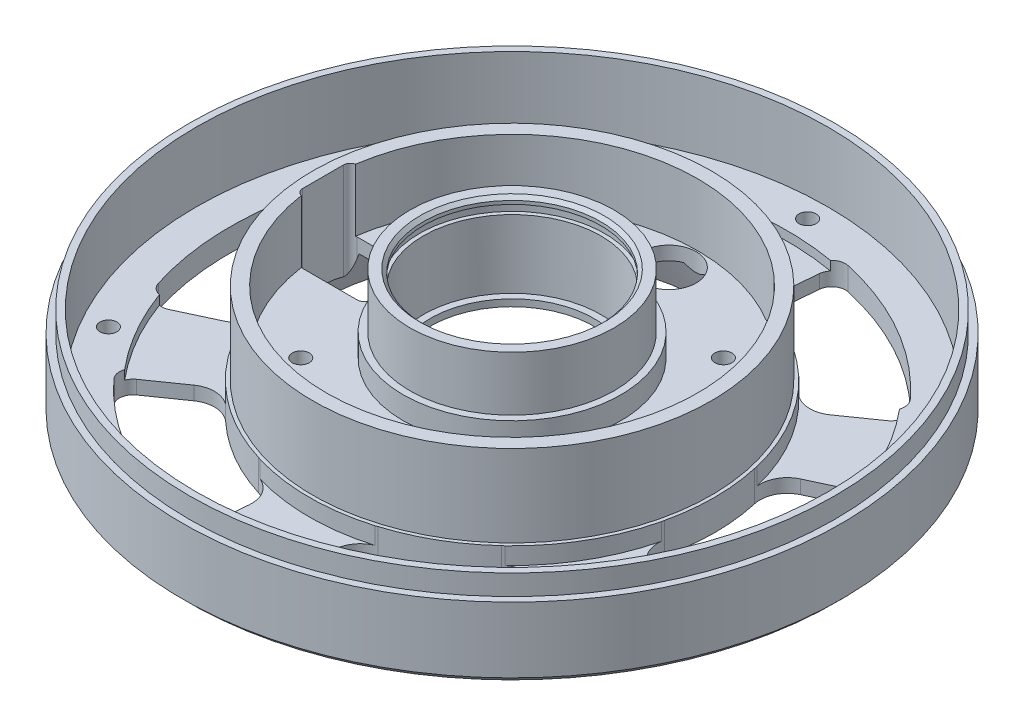
SolidWorks part; units mm, degrees
material "5052-H32"
ref_plane "Front Plane" through (0, 0, 0) normal (0, 0, 1) x (1, 0, 0)
ref_plane "Top Plane" through (0, 0, 0) normal (0, 1, 0) x (1, 0, 0)
ref_plane "Right Plane" through (0, 0, 0) normal (1, 0, 0) x (0, 0, -1)
ref_axis "Axis1" through (0, 0, 0) along (0, 1, 0)
sketch "Sketch1" plane through (0, 0, 0) normal (0, 0, 1) x (1, 0, 0)
  line L0 (0, 0) -> (0, -50000) construction
  line L1 (-13.02, 8.15) -> (-13.02, -4.15)
  line L2 (-13.02, -4.15) -> (-12.02, -4.15)
  line L4 (45.1, 8.15) -> (-45.1, 8.15) construction
  line L5 (-12.75, -4.15) -> (12.75, -4.15) construction
  line L7 (-13.02, 8.15) -> (-14.98, 8.15)
  line L8 (-14.98, 8.15) -> (-14.98, -3.15)
  line L9 (-14.98, -3.15) -> (-28.25, -3.15)
  line L10 (-12.02, -5.15) -> (-28.25, -5.15)
  line L12 (-28.25, -5.15) -> (-28.25, -3.15)
  line L13 (-29.25, 6) -> (-29.25, -6) construction
  line L16 (-12.02, -4.15) -> (-12.02, -5.15)
  dimension "D1" = 1
  dimension "D2" = 29.96
  dimension "D3" = 2
  dimension "D4" = 1
  dimension "D5" = 1
  dimension "D6" = 26.04
revolve "Revolve1" add sketch "Sketch1" angle 360 about L0
sketch "Sketch4" plane through (0, 0, 0) normal (0, 0, 1) x (1, 0, 0)
  line L1 (-29.75, -8.5) -> (-40.35, -8.5)
  line L2 (-46.35, -7.15) -> (-46.35, 3)
  line L3 (-46.35, 3) -> (-47.35, 3)
  line L4 (-47.35, 3) -> (-47.35, 0)
  line L5 (-47.35, 0) -> (-48.35, 0)
  line L6 (-48.35, 0) -> (-48.35, -9.6235)
  line L7 (-47.4735, -10.5) -> (-28.75, -10.5)
  line L8 (-28.75, -10.5) -> (-26.75, -5.15)
  line L9 (-29.75, -8.5) -> (-29.75, -6)
  line L10 (-26.75, -5.15) -> (-26.75, -3.15)
  line L12 (-48.35, -9.6235) -> (-47.4735, -10.5)
  line L13 (-45.1, 8.15) -> (-45.1, -6.15) construction
  line L14 (-46.35, -7.15) -> (-40.35, -7.15)
  line L15 (-40.35, -7.15) -> (-40.35, -8.5)
  line L16 (-45.1, -6.15) -> (45.1, -6.15) construction
  line L18 (-44.85, -7.15) -> (-44.85, -10.5) construction
  line L20 (-41.85, -7.15) -> (-41.85, -10.5) construction
  line L21 (-30.25, -6) -> (30.25, -6) construction
  line L22 (-29.75, -6) -> (-29.23, -6)
  line L23 (-29.25, -6) -> (29.25, -6) construction
  line L24 (-29.23, -6) -> (-29.23, -3.15)
  line L25 (-29.23, -3.15) -> (-26.75, -3.15)
  line L26 (28.25, -3.15) -> (-28.25, -3.15) construction
  line L27 (-39.5, -7.5) -> (39.5, -7.5) construction
  line L28 (0, 0) -> (0, 50000) construction
  line L29 (-30.25, -6) -> (-30.25, -7.5) construction
  line L33 (-28.25, -5.15) -> (28.25, -5.15) construction
  dimension "D1" = 2
  dimension "D2" = 3
  dimension "D3" = 1
  dimension "D4" = 2
  dimension "D5" = 0.5
  dimension "D6" = 1
  dimension "D7" = 1.25
  dimension "D8" = 135
  dimension "D9" = 3
  dimension "D10" = 1.5
  dimension "D11" = 1.5
  dimension "D12" = 2
  dimension "D13" = 1
  dimension "D14" = 58.46
revolve "Revolve2" add sketch "Sketch4" angle 360 about axis through (0, 0, 0) along (0, 1, 0)
sketch "Sketch6" plane through (0, 0, 0) normal (0, 0, 1) x (1, 0, 0)
  line L0 (-29.23, 6) -> (-27.23, 6)
  line L1 (-27.23, 6) -> (-27.23, -3.15)
  line L2 (-27.23, -3.15) -> (-29.23, -3.15)
  line L3 (-29.23, -3.15) -> (-29.23, 6)
  line L4 (29.25, 6) -> (-29.25, 6) construction
  line L6 (29.23, -3.15) -> (-29.23, -3.15) construction
  dimension "D1" = 2
revolve "Revolve3" add sketch "Sketch6" angle 360 about axis through (0, 0, 0) along (0, 1, 0)
sketch "Sketch7" plane through (0, 0, 0) normal (0, 0, 1) x (1, 0, 0)
  line L0 (40.35, -8.5) -> (-40.35, -8.5) construction
  line L1 (-29.58, -6) -> (-29.23, -6)
  line L2 (-29.73, -6.15) -> (-29.73, -8.5)
  line L3 (-29.73, -8.5) -> (-29.23, -8.5)
  line L4 (-29.23, -6) -> (-29.23, -8.5)
  line L5 (-29.23, 6) -> (-29.23, -6) construction
  line L6 (-29.58, -6) -> (-29.73, -6.15)
  line L7 (29.75, -8.5) -> (-29.75, -8.5) construction
  line L8 (-31.759, -6.15) -> (-25.7399, -6.15) construction
  line L13 (-30.25, -6) -> (30.25, -6) construction
  dimension "D1" = 135
  dimension "D2" = 0.5
revolve "Revolve4" add sketch "Sketch7" angle 360 about axis through (0, 0, 0) along (0, 1, 0)
sketch "Sketch8" plane through (0, -5.15, 0) normal (0, -1, 0) x (1, 0, 0)
  circle A0 centre (-15.5, 15.5) radius 3.5
  circle A1 centre (15.5, 15.5) radius 3.5
  circle A2 centre (15.5, -15.5) radius 3.5
  circle A3 centre (-15.5, -15.5) radius 3.5
  dimension "D1" = 7
sketch "Sketch10" plane through (0, 0, 0) normal (0, 0, 1) x (1, 0, 0)
  line L0 (-15.25, 0.15) -> (15.25, 0.15) construction
  line L1 (-14.98, -3.15) -> (-15.98, -3.15)
  line L2 (-14.98, -3.15) -> (-14.98, 0.15)
  line L3 (-14.98, 0.15) -> (-15.98, 0.15)
  line L4 (-15.98, -3.15) -> (-15.98, 0.15)
  line L5 (-14.98, 8.15) -> (-14.98, -3.15) construction
  line L6 (14.98, -3.15) -> (-14.98, -3.15) construction
  dimension "D1" = 1
revolve "Revolve5" add sketch "Sketch10" angle 360 about axis through (0, 0, 0) along (0, 1, 0)
sketch "Sketch12" plane through (0, 0, 0) normal (0, 1, 0) x (1, 0, 0)
  circle A0 centre (-23, 0) radius 4
  dimension "D1" = 8
  dimension "D2" = 23
extrude "Cut-Extrude2" cut sketch "Sketch12" against normal through all
pattern_circular "CirPattern3" count 4 over 360 about axis through (0, 0, 0) along (0, 1, 0) of "Cut-Extrude2"
extrude "Boss-Extrude1" add sketch "Sketch8" along normal up to surface (3.85 mm away)
hole_wizard "M3x0.5 Tapped Hole1" positions "Sketch14" profile "Sketch15" tap size "M3x0.5" standard "ANSI Metric" end condition through all
sketch "Sketch14" plane through (0, -9, 0) normal (0, -1, 0) x (-1, 0, 0)
  point P0 (-15.5, 15.5)
  point P3 (15.5, 15.5)
  point P6 (15.5, -15.5)
  point P9 (-15.5, -15.5)
cosmetic thread "Hole Thread1" parameters "D2"=3
cosmetic thread "Hole Thread2" parameters "D2"=3
cosmetic thread "Hole Thread3" parameters "D2"=3
cosmetic thread "Hole Thread4" parameters "D2"=3
sketch "Sketch15" plane through (15.5, -9, -15.5) normal (1, 0, 0) x (0, 0, -1)
  line L0 (0, 0) -> (0, 17.15)
  line L1 (0, 17.15) -> (1.25, 17.15)
  line L2 (1.25, 17.15) -> (1.25, 0)
  line L5 (1.25, 0) -> (0, 0)
  line L11 (0, -6.35) -> (0, 107.95) construction
  dimension "Thru Tap Drill Dia." = 2.5
  dimension "Thru Tap Drill Depth" = 17.15
hole_wizard "M3x0.5 Tapped Hole3" positions "Sketch19" profile "Sketch20" tap size "M3x0.5" standard "ANSI Metric" end condition through all
sketch "Sketch19" plane through (0, -10.5, 0) normal (0, -1, 0) x (-1, 0, 0)
  line L0 (0, 0) -> (0, 43.35) construction
  line L3 (0, 0) -> (-50000, 0) construction
  circle A1 centre (0, 0) radius 43.35 construction
  circle A2 centre (0, 0) radius 40.35 construction
  point P0 (0, 43.35)
  dimension "D1" = 3
  dimension "D2" = 90
sketch "Sketch20" plane through (0, -10.5, -43.35) normal (1, 0, 0) x (0, 0, -1)
  line L0 (0, 0) -> (0, 18.65)
  line L1 (0, 18.65) -> (1.25, 18.65)
  line L2 (1.25, 18.65) -> (1.25, 0.5)
  line L3 (1.25, 0.5) -> (1.75, 0)
  line L5 (1.75, 0) -> (0, 0)
  line L6 (-1.25, 0.5) -> (-1.75, 0) construction
  line L11 (0, -6.35) -> (0, 107.95) construction
  dimension "Thru Tap Drill Dia." = 2.5
  dimension "Thru Tap Drill Depth" = 18.65
  dimension "Near C'Sink Dia." = 3.5
  dimension "Near C'Sink Angle" = 90
cosmetic thread "Hole Thread7" parameters "D2"=3
pattern_circular "CirPattern4" count 6 over 360 about axis through (0, 0, 0) along (0, 1, 0) of "M3x0.5 Tapped Hole3"
sketch "Sketch24" plane through (0, -10.5, 0) normal (0, -1, 0) x (1, 0, 0)
  line L9 (-25.6489, 5.5) -> (-44.2117, 5.5)
  line L10 (-25.6489, 5.5) -> (-25.6489, -5.5)
  line L11 (-25.6489, -5.5) -> (-44.2117, -5.5)
  line L12 (-46.2117, 3.5) -> (-46.2117, -3.5)
  arc A5 (-44.2117, -5.5) -> (-46.2117, -3.5) centre (-44.2117, -3.5) cw
  arc A6 (-44.2117, 5.5) -> (-46.2117, 3.5) centre (-44.2117, 3.5) ccw
  circle A7 centre (0, 0) radius 46.35 construction
  point P5 (-25.6489, 0)
  dimension "D2" = 2
  dimension "D1" = 11
extrude "Cut-Extrude6" [suppressed] cut sketch "Sketch24" against normal up to surface (1.5 mm away)
sketch "Sketch25" plane through (0, -10.5, 0) normal (0, -1, 0) x (1, 0, 0)
  line L5 (-25.6489, 5.5) -> (-44.2117, 5.5) construction
  line L9 (-34.6807, 5.5) -> (-44.2117, 5.5)
  line L10 (-34.6807, 5.5) -> (-34.6807, -5.5)
  line L11 (-34.6807, -5.5) -> (-44.2117, -5.5)
  line L12 (-46.2117, 3.5) -> (-46.2117, -3.5)
  line L13 (-25.6489, -5.5) -> (-44.2117, -5.5) construction
  line L14 (-46.2117, 3.5) -> (-46.2117, -3.5) construction
  arc A3 (-44.2117, -5.5) -> (-46.2117, -3.5) centre (-44.2117, -3.5) cw
  arc A4 (-44.2117, 5.5) -> (-46.2117, 3.5) centre (-44.2117, 3.5) ccw
  point P12 (-46.2117, -5.5)
  dimension "D1" = 2
extrude "Cut-Extrude7" [suppressed] cut sketch "Sketch25" against normal through all
sketch "Sketch26" plane through (0, 0, 0) normal (0, 1, 0) x (1, 0, 0)
  line L0 (0, 0) -> (-50000, 0) construction
  line L1 (31.1951, 11.1252) -> (36.6728, 13.6795)
  line L2 (31.1951, -11.1252) -> (36.6728, -13.6795)
  arc A0 (39.4249, 12.47) -> (39.4249, -12.47) centre (0, 0) cw
  arc A1 (28.9857, 6.6106) -> (28.9857, -6.6106) centre (0, 0) cw
  arc A2 (28.9857, -6.6106) -> (31.1951, -11.1252) centre (32.8856, -7.5) ccw
  arc A3 (28.9857, 6.6106) -> (31.1951, 11.1252) centre (32.8856, 7.5) cw
  circle A4 centre (0, 0) radius 46.35 construction
  arc A6 (39.4249, -12.47) -> (36.6728, -13.6795) centre (37.518, -11.8669) cw
  arc A7 (39.4249, 12.47) -> (36.6728, 13.6795) centre (37.518, 11.8669) ccw
  circle A8 centre (0, 0) radius 29.23 construction
  point P12 (28.108, -9.6857)
  point P15 (28.108, 9.6857)
  point P20 (38.6807, -14.6158)
  point P26 (38.6807, 14.6158)
  dimension "D1" = 4
  dimension "D2" = 0.5
  dimension "D4" = 2
  dimension "D6" = 5
  dimension "D3" = 50
  dimension "D5" = 15
extrude "Cut-Extrude8" cut sketch "Sketch26" against normal through all both and the other way through all
pattern_circular "CirPattern5" count 6 over 360 about axis through (0, 0, 0) along (0, 1, 0) of "Cut-Extrude8"
sketch "Sketch30" plane through (0, -10.5, 0) normal (0, -1, 0) x (1, 0, 0)
  line L1 (6.6135, 5) -> (34.3769, 5)
  line L2 (6.6135, 5) -> (6.6135, -5)
  line L3 (6.6135, -5) -> (34.3769, -5)
  line L4 (34.3769, 5) -> (34.3769, -5)
  point P4 (6.6135, 0)
  dimension "D1" = 10
extrude "Cut-Extrude13" [suppressed] cut sketch "Sketch30" against normal up to surface (5.35 mm away) up to face at (-15.5, -5.15, -19)
sketch "Sketch31" plane through (0, 0, 0) normal (0, 0, 1) x (1, 0, 0)
  line L0 (0, 0) -> (0, -50000) construction
  line L1 (13.02, 8.15) -> (-13.02, 8.15) construction
  line L2 (-5.4339, 7.15) -> (-13.6, 7.15)
  line L3 (-5.4339, 7.15) -> (-5.4339, 5.85)
  line L4 (-5.4339, 5.85) -> (-13.6, 5.85)
  line L5 (-13.6, 7.15) -> (-13.6, 5.85)
  dimension "D1" = 1.3
  dimension "D2" = 1
  dimension "D3" = 27.2
revolve "Cut-Revolve1" cut sketch "Sketch31" angle 360 about L0
chamfer "Chamfer1" distance 0.5 angle 45 1 edges at (0, 8.15, 13.02)
sketch "Sketch32" plane through (0, 0, 0) normal (0, 1, 0) x (1, 0, 0)
  line L1 (-18.73, 4) -> (-26.73, 4)
  line L2 (-17.73, 3) -> (-17.73, -3)
  line L3 (-18.73, -4) -> (-26.73, -4)
  line L4 (-27.73, 3) -> (-27.73, -3)
  arc A0 (-26.73, 4) -> (-27.73, 3) centre (-26.73, 3) ccw
  arc A1 (-17.73, -3) -> (-18.73, -4) centre (-18.73, -3) cw
  arc A2 (-26.73, -4) -> (-27.73, -3) centre (-26.73, -3) cw
  arc A3 (-18.73, 4) -> (-17.73, 3) centre (-18.73, 3) cw
  circle A4 centre (0, 0) radius 27.23 construction
  circle A5 centre (0, 0) radius 27.23 construction
  point P4 (-17.73, 0)
  point P16 (-27.23, 0)
  dimension "D2" = 1
  dimension "D3" = 0.5
  dimension "D1" = 8
  dimension "D4" = 10
extrude "Cut-Extrude14" cut sketch "Sketch32" against normal through all both and the other way through all
